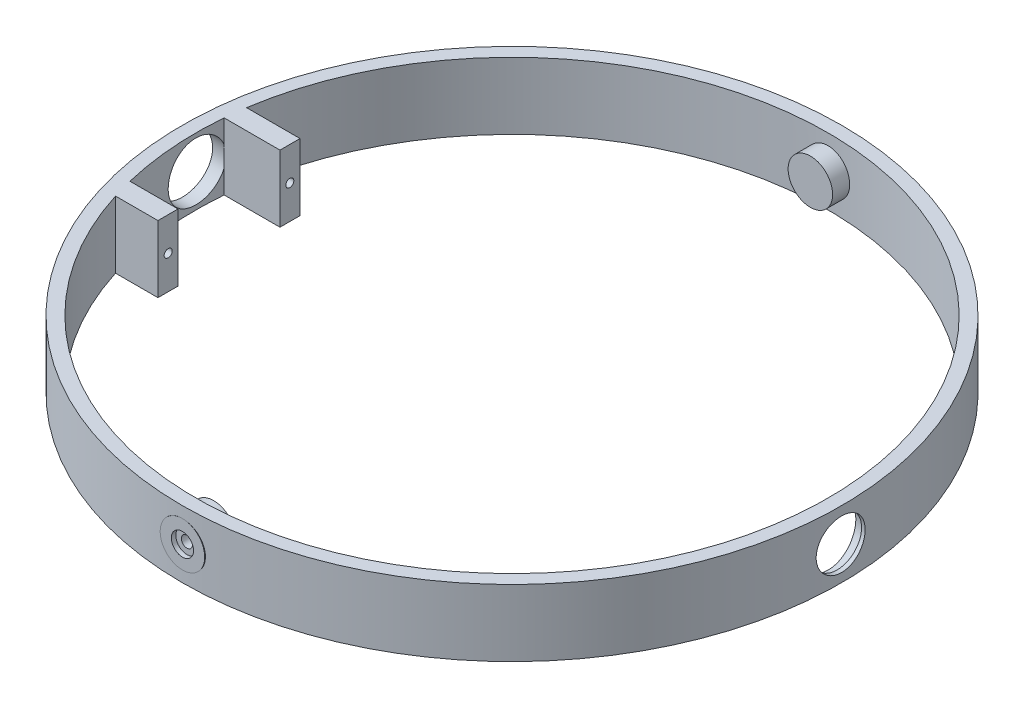
SolidWorks part; units mm, degrees
ref_plane "Front Plane" through (0, 0, 0) normal (0, 0, 1) x (1, 0, 0)
ref_plane "Top Plane" through (0, 0, 0) normal (0, 1, 0) x (1, 0, 0)
ref_plane "Right Plane" through (0, 0, 0) normal (1, 0, 0) x (0, 0, -1)
sketch "Sketch1" plane through (0, 0, 0) normal (0, 1, 0) x (1, 0, 0)
  circle A0 centre (0, 0) radius 71
  circle A1 centre (0, 0) radius 74
  dimension "D1" = 148
  dimension "D2" = 3
extrude "Boss-Extrude1" add sketch "Sketch1" along normal blind 15
sketch "Sketch2" plane through (0, 0, 0) normal (1, 0, 0) x (0, 0, -1)
  circle A0 centre (0, 7.5) radius 6.5
  dimension "D1" = 13
  dimension "D2" = 7.5
extrude "Cut-Extrude1" cut sketch "Sketch2" against normal through all and the other way blind 73
sketch "Sketch9" plane through (0, 0, 0) normal (1, 0, 0) x (0, 0, -1)
  circle A0 centre (0, 7.5) radius 5.5
  point P2 (0, 0)
  dimension "D1" = 11
  dimension "D2" = 7.5
extrude "Cut-Extrude6" cut sketch "Sketch9" along normal through all
ref_plane "Plane1" through (0, 0, 73) normal (0, 0, 1) x (1, 0, 0)
sketch "Sketch3" plane through (0, 0, 73) normal (0, 0, 1) x (1, 0, 0)
  circle A0 centre (0, 7.5) radius 5
  dimension "D1" = 10
  dimension "D2" = 7.5
extrude "Boss-Extrude2" add sketch "Sketch3" along normal blind 1 and the other way blind 6 contours A0
mirror "Mirror1" about plane through (0, 0, 0) normal (0, 0, 1) of "Boss-Extrude2"
sketch "Sketch4" plane through (0, 15, 0) normal (0, 1, 0) x (1, 0, 0)
  line L0 (-58.2, -16.8) -> (-68.9838, -16.8)
  line L1 (-58.2, -16.8) -> (-58.2, -21.3)
  line L2 (-58.2, -21.3) -> (-68.9838, -21.3)
  line L3 (-68.9838, -21.3) -> (-68.9838, -16.8)
  line L4 (-58.2, 6.1) -> (-58.2, 10.6)
  line L5 (-58.2, 6.1) -> (-70.7375, 6.1)
  line L6 (-70.7375, 6.1) -> (-70.7375, 10.6)
  line L7 (-70.7375, 10.6) -> (-58.2, 10.6)
  circle A0 centre (0, 0) radius 71 construction
  dimension "D2" = 4.5
  dimension "D3" = 4.5
extrude "Boss-Extrude3" add sketch "Sketch4" against normal up to surface (15 mm away) up to face at (0, 0, 74)
sketch "Sketch5" plane through (-58.2, 0, 0) normal (1, 0, 0) x (0, 0, -1)
  circle A0 centre (8.3, 7.5) radius 0.9
  circle A1 centre (-19, 7.5) radius 0.9
  dimension "D1" = 1.8
  dimension "D2" = 1.8
extrude "Cut-Extrude2" cut sketch "Sketch5" against normal blind 8
sketch "Sketch6" plane through (0, 0, 67) normal (0, 0, -1) x (-1, 0, 0)
  circle A0 centre (0, 7.5) radius 2.45
  dimension "D1" = 4.9
extrude "Cut-Extrude3" cut sketch "Sketch6" against normal blind 4
sketch "Sketch7" plane through (0, 0, 71) normal (0, 0, -1) x (-1, 0, 0)
  circle A0 centre (0, 7.5) radius 1.25
  dimension "D1" = 2.5
extrude "Cut-Extrude4" cut sketch "Sketch7" against normal blind 4
ref_plane "Plane2" through (0, 0, 73) normal (0, 0, -1) x (-1, 0, 0)
sketch "Sketch8" plane through (0, 0, 73) normal (0, 0, -1) x (-1, 0, 0)
  circle A0 centre (0, 7.5) radius 2.5
  dimension "D1" = 5
extrude "Cut-Extrude5" cut sketch "Sketch8" against normal blind 4
